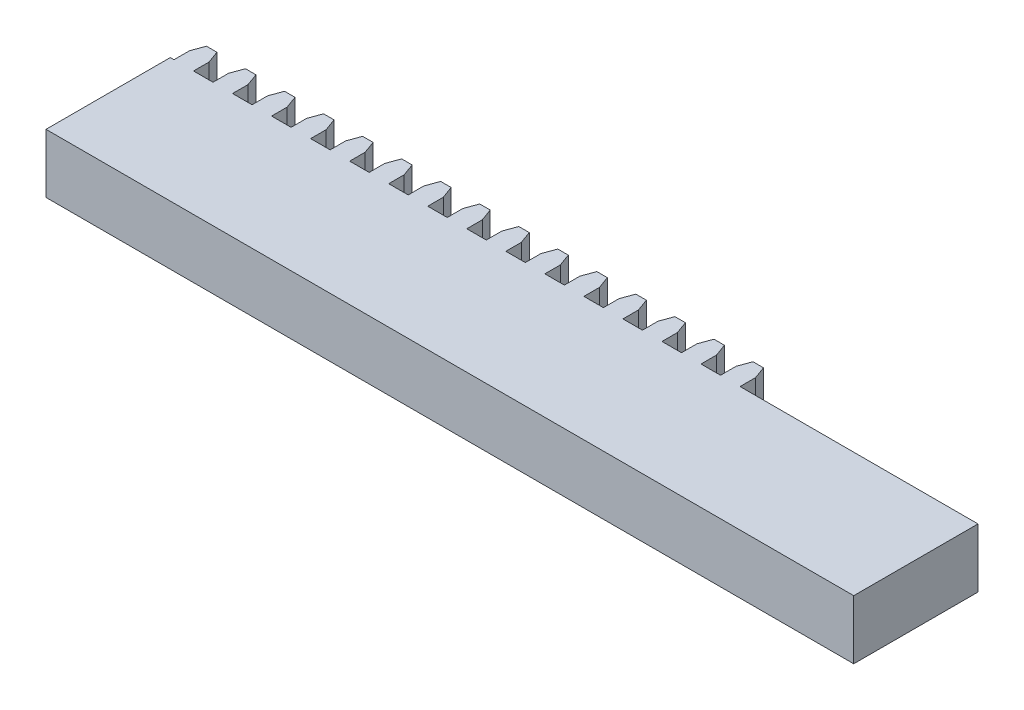
SolidWorks part; units mm, degrees
ref_plane "Front Plane" through (0, 0, 0) normal (0, 0, 1) x (1, 0, 0)
ref_plane "Top Plane" through (0, 0, 0) normal (0, 1, 0) x (1, 0, 0)
ref_plane "Right Plane" through (0, 0, 0) normal (1, 0, 0) x (0, 0, -1)
sketch "Sketch2" plane through (0, 0, 0) normal (0, 1, 0) x (1, 0, 0)
  line L0 (-1000, 0) -> (49000, 0) construction
  line L3 (0, -1000) -> (0, 49000) construction
  line L6 (-0.8429, 4.5) -> (0.8429, 4.5)
  line L7 (1.5708, 2.5) -> (1.5708, 0)
  line L8 (-1.5712, 2.5001) -> (-1.5712, 0)
  line L55 (0.8429, 4.5) -> (1.5708, 2.5)
  line L58 (-0.8429, 4.5) -> (-1.5712, 2.5001)
  line L509 (-65, 0) -> (65, 0)
  line L510 (-65, 0) -> (-65, -20)
  line L511 (-65, -20) -> (65, -20)
  line L512 (65, 0) -> (65, -20)
  point P1 (0, -20)
  point P8 (0, 4.5)
  dimension "D3" = 2
  dimension "D4" = 20
  dimension "D7" = 130
  dimension "D9" = 20
  dimension "D1" = 3.142
  dimension "D2" = 2.5
  dimension "D5" = 4.5
extrude "Boss-Extrude1" add sketch "Sketch2" along normal blind 9.5 contours L512 L509 L510 L511 region at (0, 0, 10)
extrude "Boss-Extrude2" add sketch "Sketch2<5>" along normal up to surface (9.5 mm away) contours L8 L509 L7 L55 L6 L58 region at (-0.0002, 0, -2.0682) up to face at (0, 9.5, 10)
sketch "Sketch2<5>" plane through (0, 0, 0) normal (0, 1, 0) x (1, 0, 0) same geometry as "Sketch2"
pattern_linear "LPattern1" count 11 spacing 6.2832 along (-1, 0, 0) count 5 spacing 6.2832 along (1, 0, 0) of "Boss-Extrude2"
